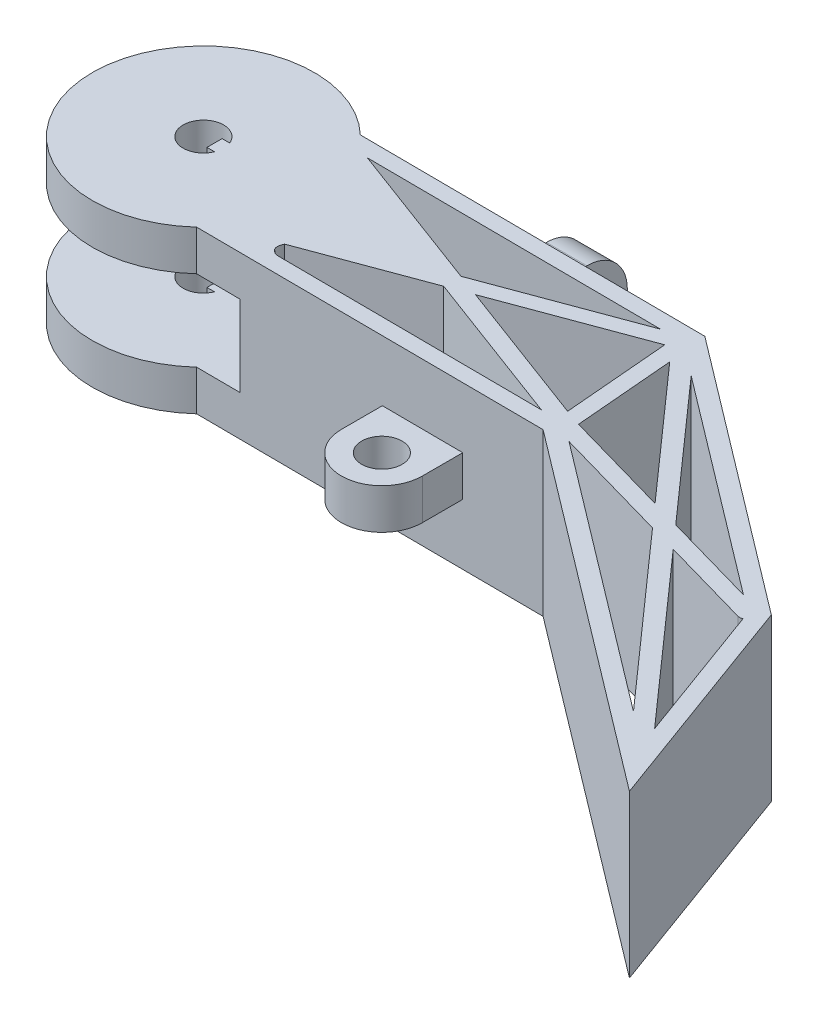
SolidWorks part; units mm, degrees
ref_plane "Front Plane" through (0, 0, 0) normal (0, 0, 1) x (1, 0, 0)
ref_plane "Top Plane" through (0, 0, 0) normal (0, 1, 0) x (1, 0, 0)
ref_plane "Right Plane" through (0, 0, 0) normal (1, 0, 0) x (0, 0, -1)
sketch "Sketch2" plane through (0, 0, 0) normal (0, 1, 0) x (1, 0, 0)
  line L0 (-86.363, -5.4396) -> (-1.4058, -5.4396) construction
  line L1 (-2.3879, -18.8413) -> (53.579, -61.2476)
  line L2 (53.579, -61.2476) -> (40.7275, -26.11)
  line L3 (-56.8308, 6.8962) -> (-2.3879, 6.5587)
  line L4 (40.7275, -26.11) -> (-2.3879, 6.5587)
  line L5 (-65.9872, -6.8458) -> (-67.1778, -6.8458)
  line L6 (-57.1449, -18.5018) -> (-2.3879, -18.8413)
  line L7 (-67.1778, -6.8458) -> (-67.1778, -4.4645)
  line L8 (-67.1778, -4.4645) -> (-65.9872, -4.4645)
  arc A0 (-57.1449, -18.5018) -> (-56.8308, 6.8962) centre (-68.9305, -5.6551) cw
  arc A1 (-65.9872, -4.4645) -> (-65.9872, -6.8458) centre (-68.9305, -5.6551) ccw
  point P15 (-67.1778, -5.6551)
  dimension "D4" = 1.1906
  dimension "D1" = 6.35
  dimension "D2" = 2.3813
  dimension "D3" = 25.4
extrude "Boss-Extrude4" add sketch "Sketch2" along normal blind 12.7
sketch "Sketch4" plane through (0, 12.7, 0) normal (0, 1, 0) x (1, 0, 0)
  circle A0 centre (-68.9305, -5.6551) radius 17.6534
extrude "Cut-Extrude1" cut sketch "Sketch4" against normal blind 6.35
sketch "Triangleout" plane through (0, 6.35, 0) normal (0, 1, 0) x (1, 0, 0)
  line L0 (-58.1063, -19.5103) -> (-49.8091, -19.5103)
  line L1 (-49.8091, -19.5103) -> (-52.889, -13.0249)
  line L2 (-52.889, -13.0249) -> (-58.1063, -19.5103)
  arc A0 (-56.8245, -18.5038) -> (-56.5145, 6.8942) centre (-68.9305, -5.6551) ccw construction
extrude "Cut-Extrude2" cut sketch "Triangleout" along normal blind 6.35
mirror "Mirror3" about plane through (-68.9305, 12.7, 5.6551) normal (0, -1, 0) of "Cut-Extrude2", "Cut-Extrude1", "Boss-Extrude4"
sketch "Sketch5" plane through (0, 25.4, 0) normal (0, 1, 0) x (1, 0, 0)
  line L0 (-1.5273, -16.3066) -> (-3.2484, 4.024) construction
  line L1 (48.2252, -54.0043) -> (-3.2484, 4.024)
  line L2 (47.1532, -43.6788) -> (-2.3879, -6.1413) construction
  line L3 (-57.1291, -15.9619) -> (-3.2484, 4.024)
  line L4 (53.579, -61.2476) -> (40.7275, -26.11) construction
  line L5 (-56.9899, -5.971) -> (-2.3879, -6.1413) construction
  line L6 (-57.1469, -18.67) -> (-56.8329, 6.7281) construction
  line L7 (-56.8466, 4.3563) -> (-1.5273, -16.3066)
  line L8 (-1.5273, -16.3066) -> (38.5985, -27.6836)
  line L10 (-56.6874, -17.1526) -> (-3.6217, 2.531)
  line L11 (47.2751, -54.847) -> (-3.6217, 2.531)
  line L12 (-57.2909, 3.1665) -> (-1.9234, -17.5144)
  line L13 (-1.9234, -17.5144) -> (38.252, -28.9054)
  line L14 (-57.5708, -14.7712) -> (-2.8752, 5.517)
  line L15 (49.1753, -53.1615) -> (-2.8752, 5.517)
  line L16 (-56.4022, 5.546) -> (-1.1312, -15.0988)
  line L17 (-1.1312, -15.0988) -> (38.9449, -26.4618)
  line L18 (-1.5273, -16.3066) -> (-3.2484, 4.024)
  line L19 (-0.2618, -16.1995) -> (-1.983, 4.1311)
  line L20 (-2.7928, -16.4137) -> (-4.5139, 3.9169)
  line L28 (-3.2484, 4.024) -> (-56.8466, 4.3563)
  line L29 (38.5985, -27.6836) -> (-3.2484, 4.024)
  line L30 (48.2252, -54.0043) -> (38.5985, -27.6836)
  line L31 (-1.5273, -16.3066) -> (48.2252, -54.0043)
  line L32 (-57.1291, -15.9619) -> (-1.5273, -16.3066)
  line L33 (-3.2484, 4.024) -> (-56.8466, 4.3563)
  line L34 (38.5985, -27.6836) -> (-3.2484, 4.024)
  line L35 (48.2252, -54.0043) -> (38.5985, -27.6836)
  line L36 (-1.5273, -16.3066) -> (48.2252, -54.0043)
  line L37 (-57.1291, -15.9619) -> (-1.5273, -16.3066)
  arc A0 (-56.6874, -17.1526) -> (-57.5708, -14.7712) centre (-57.1291, -15.9619) cw
  arc A1 (47.2751, -54.847) -> (49.1753, -53.1615) centre (48.2252, -54.0043) ccw
  arc A2 (-57.2909, 3.1665) -> (-56.4022, 5.546) centre (-56.8466, 4.3563) cw
  arc A3 (38.252, -28.9054) -> (38.9449, -26.4618) centre (38.5985, -27.6836) ccw
  arc A4 (-0.2618, -16.1995) -> (-2.7928, -16.4137) centre (-1.5273, -16.3066) cw
  arc A5 (-1.983, 4.1311) -> (-4.5139, 3.9169) centre (-3.2484, 4.024) ccw
  arc A7 (-57.1469, -18.67) -> (-56.8329, 6.7281) centre (-69.6889, -5.814) ccw
  spline S0 degree 1 poles (-57.1291, -15.9619) (-56.8466, 4.3563) knots 0 0 1 1
  spline S1 degree 2 poles (-47.0814, -16.0242) (-48.6847, -15.466) (-47.9144, -13.8984) knots 0 0 0 1 1 1
  dimension "D1" = 2.54
  dimension "D2" = 1.27
  dimension "D3" = 1.27
  dimension "D4" = 1.27
  dimension "D5" = 1.27
extrude "Cut-Extrude5" cut sketch "Sketch5" against normal through all contours L10 L37 L12 | L14 L33 L16 | L16 L20 L10 | A3 L13 L15 L35 | L13 L36 L11 | L17 L34 L15 | L19 L17 L11 region at (36.7581, 25.4, 34.9291) region at (21.2892, 25.4, 30.7012) region at (4.8128, 25.4, 11.6946) region at (19.5715, 25.4, 15.6129) region at (-28.9199, 25.4, 13.075) region at (-11.1296, 25.4, 5.9841) region at (-29.8963, 25.4, -1.3164)
sketch3d "3DSketch1"
  point P0 (-32.4816, 11.0258, -6.7453)
sketch3d "3DSketch2"
  point P0 (-24.5304, 25.4, -6.696)
sketch3d "3DSketch3"
  point P0 (-56.1674, 15.0984, -6.8921)
ref_plane "Plane3" through (-30.7674, 0, 0) normal (-1, 0, 0) x (0, 0, 1)
sketch "Sketch9" plane through (-30.7674, 0, 0) normal (-1, 0, 0) x (0, 0, 1)
  line L0 (-13.2442, 19.05) -> (-6.8942, 19.05)
  line L2 (-6.8942, 19.05) -> (-6.8942, 6.35) construction
  line L3 (-6.8942, 19.05) -> (-6.8942, 6.35)
  line L5 (-6.8942, 6.35) -> (-13.2442, 6.35)
  arc A0 (-13.2442, 19.05) -> (-13.2442, 6.35) centre (-13.2442, 12.7) ccw
  circle A1 centre (-13.2442, 12.7) radius 3.175
  point P0 (-6.8942, 12.7)
  dimension "D2" = 6.35
  dimension "D3" = 6.35
  dimension "D1" = 6.35
extrude "Boss-Extrude6" add sketch "Sketch9" along normal blind 3.175 and the other way blind 3.175 separate body
sketch3d "3DSketch4"
  point P0 (0, 0, 0)
ref_plane "Plane4" through (0, 12.7, 0) normal (0, -1, 0) x (1, 0, 0)
sketch "Sketch10" plane through (0, 12.7, 0) normal (0, -1, 0) x (1, 0, 0)
  line L0 (-27.7879, 18.6838) -> (-15.0879, 18.7626)
  line L1 (-57.1449, 18.5018) -> (-2.3879, 18.8413) construction
  line L2 (-15.0879, 18.7626) -> (-15.0879, 25.1126)
  line L3 (-27.7879, 25.1126) -> (-27.7879, 18.6838)
  arc A0 (-27.7879, 25.1126) -> (-15.0879, 25.1126) centre (-21.4379, 25.1126) cw
  circle A1 centre (-21.4379, 25.1126) radius 3.175
  dimension "D1" = 6.35
  dimension "D2" = 6.35
  dimension "D3" = 6.35
  dimension "D4" = 19.05
extrude "Boss-Extrude7" add sketch "Sketch10" along normal blind 3.175 and the other way blind 3.175
sketch3d "3DSketch5"
  point P0 (-51.9133, 18.2273, 9.444)
ref_plane "Plane5" through (-87.4733, 0, 0) normal (-1, 0, 0) x (0, 0, 1)
